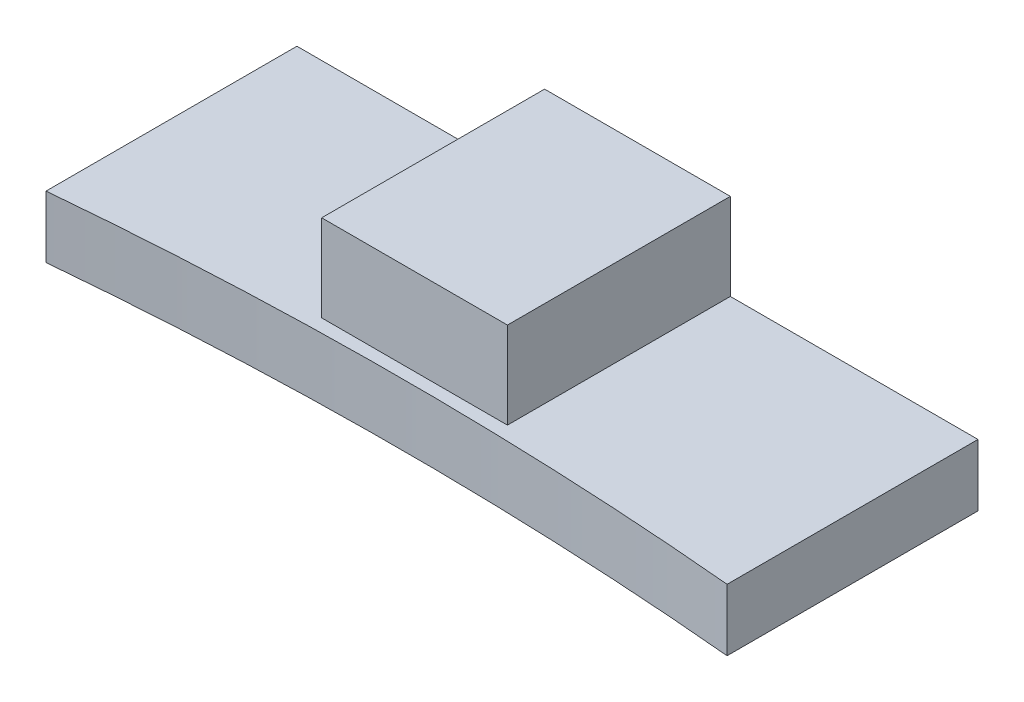
SolidWorks part; units mm, degrees
ref_plane "Front Plane" through (0, 0, 0) normal (0, 0, 1) x (1, 0, 0)
ref_plane "Top Plane" through (0, 0, 0) normal (0, 1, 0) x (1, 0, 0)
ref_plane "Right Plane" through (0, 0, 0) normal (1, 0, 0) x (0, 0, -1)
sketch "Sketch1" plane through (0, 0, 0) normal (0, 1, 0) x (1, 0, 0)
  line L0 (0, 0) -> (0, 20.2631)
  line L1 (0, 20.2631) -> (55, 20.2631)
  line L2 (55, 20.2631) -> (55, 0)
  arc A0 (0, 0) -> (55, 0) centre (27.5, -298.7369) cw
  dimension "D1" = 300
  dimension "D2" = 55
  dimension "D4" = 319
extrude "Boss-Extrude1" add sketch "Sketch1" along normal blind 5
sketch "Sketch2" plane through (0, 5, 0) normal (0, 1, 0) x (1, 0, 0)
  line L0 (55, 20.2631) -> (0, 20.2631) construction
  line L1 (20, 20.2631) -> (35, 20.2631)
  line L2 (20, 20.2631) -> (20, 2.2631)
  line L3 (20, 2.2631) -> (35, 2.2631)
  line L4 (35, 20.2631) -> (35, 2.2631)
  line L5 (0, 20.2631) -> (0, 0) construction
  dimension "D1" = 15
  dimension "D2" = 20
  dimension "D3" = 18
extrude "Boss-Extrude2" add sketch "Sketch2" along normal blind 7
sketch "Sketch3" plane through (0, 0, -20.2631) normal (0, 0, -1) x (-1, 0, 0)
  line L0 (-55, 0) -> (0, 0) construction
  line L1 (-35, 12) -> (-35, 5) construction
  circle A0 centre (-27.5, 6.5) radius 4.5
  dimension "D1" = 9
  dimension "D2" = 6.5
  dimension "D3" = 7.5
extrude "Cut-Extrude2" cut sketch "Sketch3" against normal blind 4
hole_wizard "Tap Drill for M8x1.25 Tap1" positions "Sketch5" profile "Sketch4" hole size "M8x1.25" standard "ANSI Metric"
sketch "Sketch5" plane through (0, 0, -16.2631) normal (0, 0, -1) x (-1, 0, 0)
  point P0 (-27.5, 6.5)
sketch "Sketch4" plane through (27.5, 6.5, -16.2631) normal (1, 0, 0) x (0, 1, 0)
  line L0 (0, 0) -> (0, 8)
  line L1 (0, 8) -> (3.4, 8)
  line L2 (3.4, 8) -> (3.4, 0)
  line L5 (3.4, 0) -> (0, 0)
  line L10 (0, 8) -> (-3.4, 8) construction
  line L11 (0, -6.35) -> (0, 107.95) construction
  dimension "Hole Dia." = 6.8
  dimension "Hole Depth" = 8
  dimension "Drill Angle" = 180
